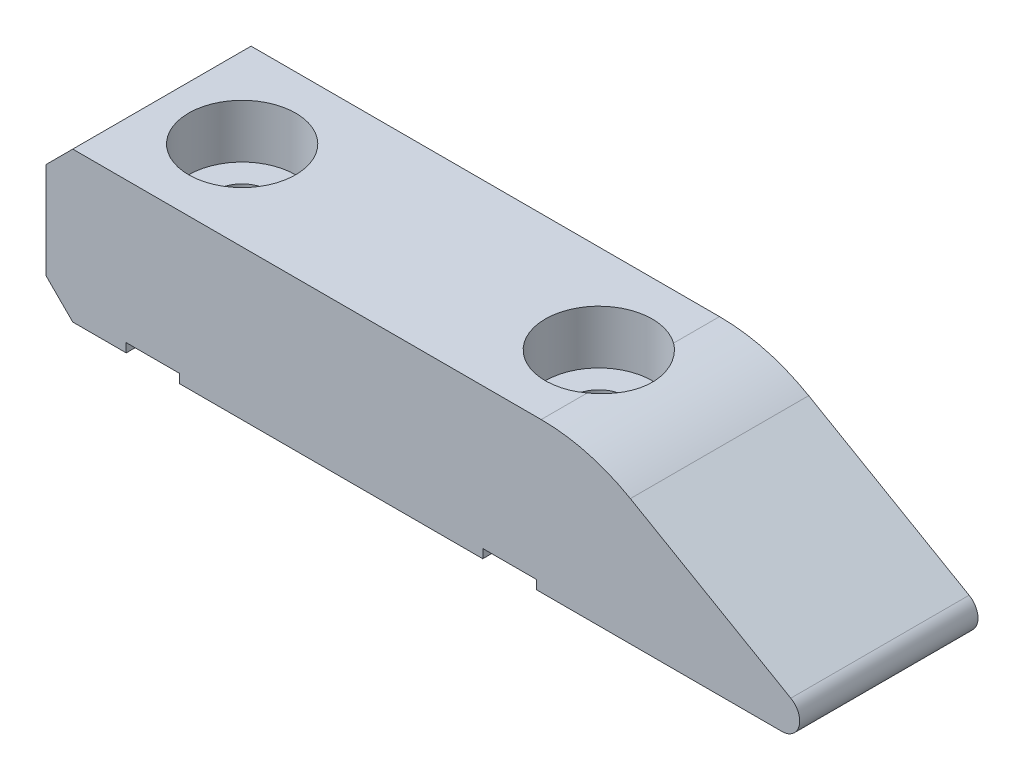
SolidWorks part; units mm, degrees
material "POM 乙缩醛共聚物"
ref_plane "前视基准面" through (0, 0, 0) normal (0, 0, 1) x (1, 0, 0)
ref_plane "上视基准面" through (0, 0, 0) normal (0, 1, 0) x (1, 0, 0)
ref_plane "右视基准面" through (0, 0, 0) normal (1, 0, 0) x (0, 0, -1)
sketch "草图1" plane through (0, 0, 0) normal (0, 0, 1) x (1, 0, 0)
  line L0 (0, 0) -> (-14.5492, 8.4)
  line L1 (-14.5492, 8.4) -> (-45, 8.4)
  line L2 (-45, 8.4) -> (-45, 0)
  line L3 (-45, 0) -> (0, 0)
  dimension "D1" = 45
  dimension "D2" = 30
  dimension "D3" = 8.4
  dimension "D4" = 30.4508
extrude "凸台-拉伸1" add sketch "草图1" along normal mid plane 10
sketch "草图2" plane through (0, 8.4, 0) normal (0, 1, 0) x (1, 0, 0)
  line L0 (-45, -5) -> (-45, 5) construction
  circle A0 centre (-39, 0) radius 1.5
  circle A1 centre (-19, 0) radius 1.5
  dimension "D1" = 20
  dimension "D2" = 3
  dimension "D3" = 6
extrude "切除-拉伸1" cut sketch "草图2" against normal through all
sketch "草图3" plane through (0, 8.4, 0) normal (0, 1, 0) x (1, 0, 0)
  circle A0 centre (-39, 0) radius 3
  circle A1 centre (-19, 0) radius 3
  dimension "D1" = 6
extrude "切除-拉伸2" cut sketch "草图3" against normal blind 3
fillet "圆角1" radius 10 1 edges at (-14.5492, 8.4, 0)
fillet "圆角2" radius 1 1 edges at (0, 0, 0)
chamfer "倒角1" distance 1.5 angle 45 2 edges at (-45, 0, 0) (-45, 8.4, 0)
sketch "草图4" plane through (0, 0, 0) normal (0, -1, 0) x (1, 0, 0)
  line L0 (-43.5, 5) -> (-3.7321, 5) construction
  line L1 (-40.5, -5) -> (-37.5, -5)
  line L2 (-40.5, -5) -> (-40.5, 5)
  line L3 (-40.5, 5) -> (-37.5, 5)
  line L4 (-37.5, -5) -> (-37.5, 5)
  line L5 (-40.5, -5) -> (-37.5, 5) construction
  line L6 (-40.5, 5) -> (-37.5, -5) construction
  line L8 (-20.5053, -5) -> (-17.4947, -5)
  line L9 (-20.5053, -5) -> (-20.5053, 5)
  line L10 (-20.5053, 5) -> (-17.4947, 5)
  line L11 (-17.4947, -5) -> (-17.4947, 5)
  line L12 (-20.5053, -5) -> (-17.4947, 5) construction
  line L13 (-20.5053, 5) -> (-17.4947, -5) construction
  point P0 (-39, 0)
  point P8 (-19, 0)
extrude "切除-拉伸3" cut sketch "草图4" against normal blind 0.5
